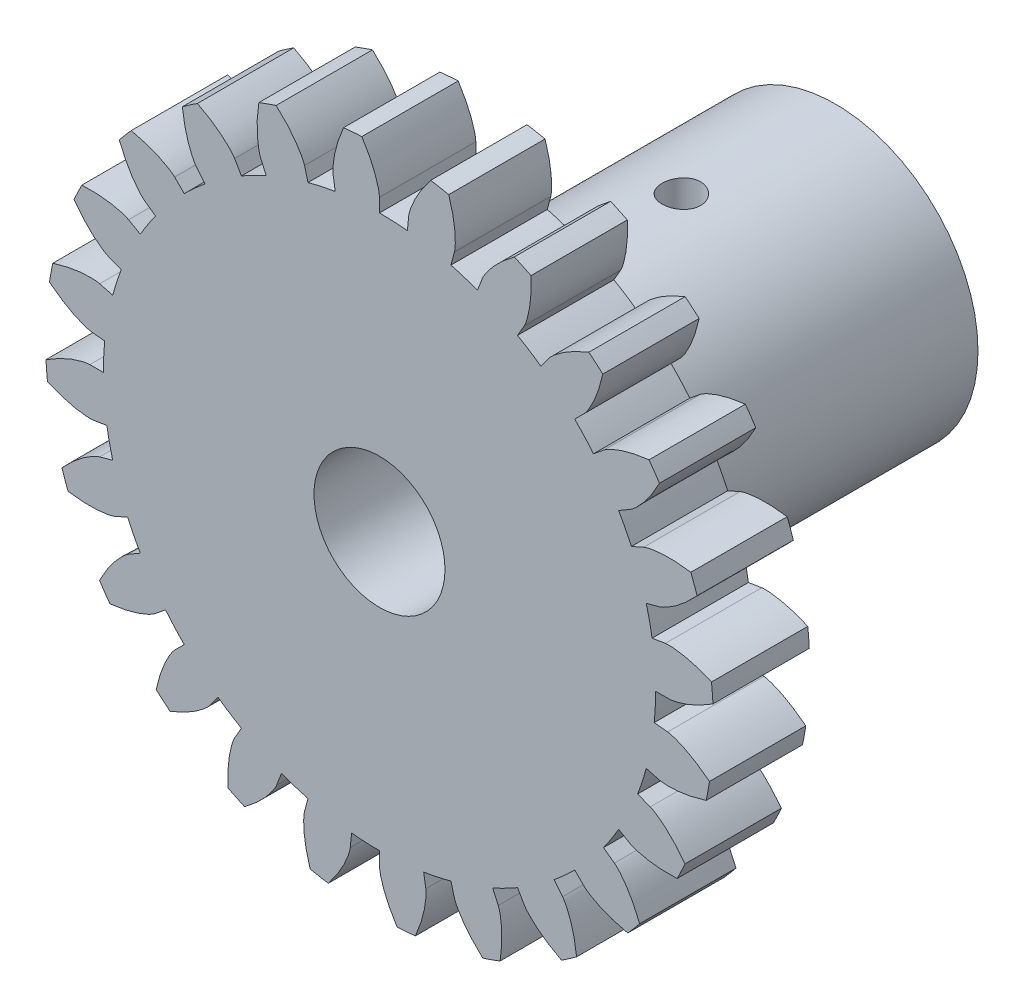
SolidWorks part; units mm, degrees
material "7075-O (SS)"
ref_plane "Front" through (0, 0, 0) normal (0, 0, 1) x (1, 0, 0)
ref_plane "Top" through (0, 0, 0) normal (0, 1, 0) x (1, 0, 0)
ref_plane "Right" through (0, 0, 0) normal (1, 0, 0) x (0, 0, -1)
sketch "ｽｹｯﾁ1" plane through (0, 0, 0) normal (0, 0, 1) x (1, 0, 0)
  line L0 (22.5526, 0) -> (0, 0) construction
  line L1 (22.5526, 0) -> (21.5, 0)
  line L2 (0, 0) -> (25.9668, -1.3136)
  circle A0 centre (0, 0) radius 22.5526 construction
  circle A1 centre (0, 0) radius 21.5 construction
  circle A2 centre (0, 0) radius 24 construction
  circle A3 centre (0, 0) radius 26
  arc A4 (21.5, 0) -> (21.4725, -1.0863) centre (0, 0) cw
  arc A5 (23.9973, 0.3577) -> (23.9693, -1.2126) centre (0, 0) cw
  spline S0 degree 4 poles (22.5526, 0) (22.5874, 0.0011) (22.6567, 0.0054) (22.8505, 0.0283) (23.2156, 0.0999) (23.764, 0.2576) (24.4933, 0.5458) (25.3932, 1.0005) (26.3919, 1.6314) (27.421, 2.4222) (28.4509, 3.3688) (29.4028, 4.3935) (30.2783, 5.4838) (31.1188, 6.6866) (32.0583, 8.2419) (33.024, 10.183) (33.9312, 12.5326) (34.6768, 15.2302) (35.1717, 17.9843) (35.4277, 20.7703) (35.4563, 23.5676) (35.2683, 26.3585) (34.9241, 28.7814) (34.5417, 30.6653) (34.2091, 32.0222) (33.9364, 33.0347) (33.6419, 34.0391) (33.318, 35.0387) (32.9699, 36.023) (32.6584, 36.8453) (32.4056, 37.4843) (32.1525, 38.0917) (31.9408, 38.5845) (31.6913, 39.1427) (31.5261, 39.5026) (31.2539, 40.0814) (31.0342, 40.5277) (30.7638, 41.0681) (30.5147, 41.5456) (30.242, 42.0581) (29.9755, 42.5406) (29.7632, 42.9175) (29.6249, 43.1564) (29.5531, 43.2804) knots 0 0 0 0 0 0.002802 0.005604 0.015718 0.02996 0.048734 0.068727 0.096889 0.125051 0.153212 0.181374 0.209535 0.237696 0.271429 0.327752 0.384075 0.440398 0.496721 0.553044 0.609367 0.66569 0.722013 0.750174 0.764255 0.778336 0.806497 0.834659 0.84874 0.86282 0.876901 0.890982 0.900036 0.909091 0.920455 0.931818 0.943182 0.954545 0.965909 0.977273 0.988636 1 1 1 1 1 construction
  spline S1 degree 4 poles (22.5526, 0) (22.5874, 0.0011) (22.6567, 0.0054) (22.8505, 0.0283) (23.2156, 0.0999) (23.764, 0.2576) (24.4933, 0.5458) (25.3932, 1.0005) (26.3919, 1.6314) (27.421, 2.4222) (28.4509, 3.3688) (29.4028, 4.3935) (30.2783, 5.4838) (31.1188, 6.6866) (32.0583, 8.2419) (33.024, 10.183) (33.9312, 12.5326) (34.6768, 15.2302) (35.1717, 17.9843) (35.4277, 20.7703) (35.4563, 23.5676) (35.2683, 26.3585) (34.9241, 28.7814) (34.5417, 30.6653) (34.2091, 32.0222) (33.9364, 33.0347) (33.6419, 34.0391) (33.318, 35.0387) (32.9699, 36.023) (32.6584, 36.8453) (32.4056, 37.4843) (32.1525, 38.0917) (31.9408, 38.5845) (31.7564, 38.9971) (31.6714, 39.1846) (31.6289, 39.2774) knots 0 0 0 0 0 0.002802 0.005604 0.015718 0.02996 0.048734 0.068727 0.096889 0.125051 0.153212 0.181374 0.209535 0.237696 0.271429 0.327752 0.384075 0.440398 0.496721 0.553044 0.609367 0.66569 0.722013 0.750174 0.764255 0.778336 0.806497 0.834659 0.84874 0.86282 0.876901 0.890982 0.900036 0.909091 0.909091 0.909091 0.909091 0.909091
  dimension "歯先円直径" = 52
  dimension "基礎円直径" = 45.1052
  dimension "基礎ピッチ円直径" = 48
  dimension "全歯たけ" = 4.5
  dimension "基準ピッチ/4" = 1.5708
sketch "ｽｹｯﾁ3" plane through (0, 0, 0) normal (0, 0, 1) x (1, 0, 0)
  circle A0 centre (0, 0) radius 26 construction
  circle A1 centre (0, 0) radius 26
extrude "ﾎﾞｽ - 押し出し2" add sketch "ｽｹｯﾁ3" along normal blind 7.5
sketch "ｽｹｯﾁ4" plane through (0, 0, 0) normal (0, 0, 1) x (1, 0, 0)
  line L0 (0, 0) -> (25.9668, -1.3136) construction
  line L1 (22.5526, 0) -> (21.5, 0) construction
  line L2 (21.4725, -1.0863) -> (25.9668, -1.3136)
  line L3 (22.5526, 0) -> (21.5, 0)
  arc A1 (21.4725, -1.0863) -> (21.5, 0) centre (0, 0) ccw construction
  circle A2 centre (0, 0) radius 26 construction
  arc A3 (21.4725, -1.0863) -> (21.5, 0) centre (0, 0) ccw
  arc A4 (25.9668, -1.3136) -> (25.9637, 1.373) centre (0, 0) ccw
  spline S1 degree 4 poles (15.1862, -999.773) (16.9514, 36.3954) (19.0933, 0.7282) (21.1742, -0.3006) (23.2156, 0.0999) (23.764, 0.2576) (24.4933, 0.5458) (25.3932, 1.0005) (26.3919, 1.6314) (27.421, 2.4222) (28.4509, 3.3688) (29.4028, 4.3935) (30.2783, 5.4838) (31.1188, 6.6866) (32.0583, 8.2419) (33.024, 10.183) (33.9312, 12.5326) (34.6768, 15.2302) (35.1717, 17.9843) (35.4277, 20.7703) (35.4563, 23.5676) (35.2683, 26.3585) (34.9241, 28.7814) (34.5417, 30.6653) (34.2091, 32.0222) (33.9364, 33.0347) (33.6419, 34.0391) (33.318, 35.0387) (32.9699, 36.023) (32.6584, 36.8453) (32.4056, 37.4843) (32.1525, 38.0917) (31.3467, 39.9673) (29.663, 43.4627) (43.99, 11.7586) (-384.9057, 948.343) knots -0.13757 -0.13757 -0.13757 -0.13757 -0.13757 0.002802 0.005604 0.015718 0.02996 0.048734 0.068727 0.096889 0.125051 0.153212 0.181374 0.209535 0.237696 0.271429 0.327752 0.384075 0.440398 0.496721 0.553044 0.609367 0.66569 0.722013 0.750174 0.764255 0.778336 0.806497 0.834659 0.84874 0.86282 0.876901 0.890982 0.900036 1.038953 1.038953 1.038953 1.038953 1.038953 only from (22.5526, 0) to (31.6289, 39.2774) construction
  spline S2 degree 4 poles (22.5526, 0) (22.5874, 0.0011) (22.6567, 0.0054) (22.8505, 0.0283) (23.2156, 0.0999) (23.764, 0.2576) (24.4933, 0.5458) (25.1482, 0.8767) (25.6277, 1.1589) (25.9005, 1.3322) (25.9637, 1.373) knots 0 0 0 0 0 0.002802 0.005604 0.015718 0.02996 0.048734 0.068727 0.074792 0.074792 0.074792 0.074792 0.074792
extrude "ｶｯﾄ - 押し出し2" cut sketch "ｽｹｯﾁ4" along normal through all
pattern_circular "円形ﾊﾟﾀｰﾝ1" count 24 over 360 about axis through (0, 0, 7.5) along (0, 0, -1) of "ｶｯﾄ - 押し出し2"
mirror "ﾐﾗｰ1" about plane through (21.4725, -1.0863, 7.5) normal (0.0505, 0.9987, 0) of "円形ﾊﾟﾀｰﾝ1"
sketch "ｽｹｯﾁ5" plane through (0, 0, 7.5) normal (0, 0, 1) x (1, 0, 0)
  circle A0 centre (0, 0) radius 5.1
  dimension "D1" = 10.2
extrude "ｶｯﾄ - 押し出し3" cut sketch "ｽｹｯﾁ5" against normal through all
sketch "ｽｹｯﾁ7" plane through (0, 0, 0) normal (0, 0, -1) x (-1, 0, 0)
  circle A0 centre (0, 0) radius 11.1
  circle A1 centre (0, 0) radius 5.1
  circle A2 centre (0, 0) radius 5.1 construction
  dimension "D1" = 6
extrude "ﾎﾞｽ - 押し出し3" add sketch "ｽｹｯﾁ7" along normal blind 28
sketch "ｽｹｯﾁ8" plane through (0, 0, 0) normal (0, 1, 0) x (1, 0, 0)
  line L0 (0, 0) -> (0, 28) construction
  line L1 (5.1, 28) -> (-5.1, 28) construction
  line L2 (0, 0) -> (0, -7.5) construction
  line L3 (-15.2028, -7.5) -> (-13.5909, -7.5) construction
  circle A0 centre (0, 16) radius 1.5
  dimension "D1" = 3
  dimension "D2" = 23.5
extrude "ｶｯﾄ - 押し出し4" cut sketch "ｽｹｯﾁ8" against normal through all both and the other way through all
equation "\"モジュール\"= 2"
equation "\"歯数\"= 24"
equation "\"圧力角\"= 20"
equation "\"歯幅\"= 7.5"
equation "\"D1@ﾎﾞｽ - 押し出し2\"=\"歯幅\""
equation "\"D1@円形ﾊﾟﾀｰﾝ1\"=\"歯数\""
equation "\"歯先円直径@ｽｹｯﾁ1\"=(\"歯数\"+2)*(\"モジュール\")"
equation "\"基礎円直径@ｽｹｯﾁ1\"=\"歯数\"*\"モジュール\"*cos(\"圧力角\")"
equation "\"全歯たけ@ｽｹｯﾁ1\"= \"モジュール\" * 2.25"
equation "\"基礎ピッチ円直径@ｽｹｯﾁ1\"=\"歯数\"*\"モジュール\""
equation "\"基準ピッチ/4@ｽｹｯﾁ1\" = PI * \"モジュール\" / 4"
